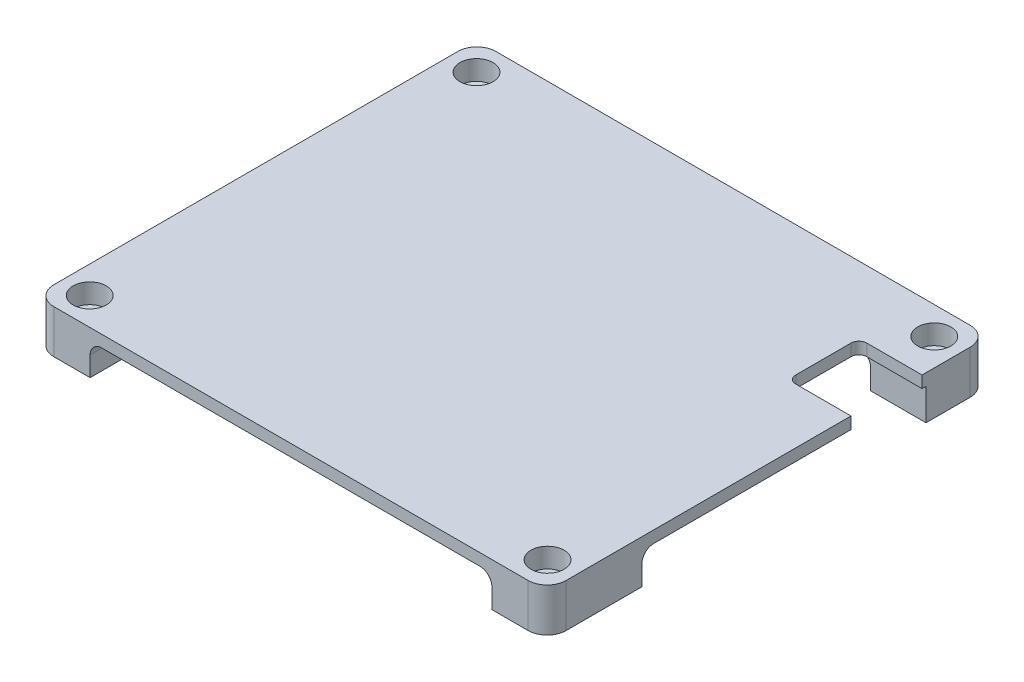
SolidWorks part; units mm, degrees
ref_plane "Front Plane" through (0, 0, 0) normal (0, 0, 1) x (1, 0, 0)
ref_plane "Top Plane" through (0, 0, 0) normal (0, 1, 0) x (1, 0, 0)
ref_plane "Right Plane" through (0, 0, 0) normal (1, 0, 0) x (0, 0, -1)
sketch "Sketch2" plane through (0, 0, 0) normal (0, 1, 0) x (1, 0, 0)
  line L0 (-22.55, -25.6) -> (-22.55, 25.6) construction
  line L1 (40.05, -28.1) -> (-40.1, -28.1) construction
  line L2 (42.55, -25.6) -> (42.55, 25.6) construction
  line L3 (40.05, 28.1) -> (-40.1, 28.1) construction
  line L4 (-22.55, -25.6) -> (-22.55, 25.6) construction
  line L5 (40.05, -28.1) -> (-20.05, -28.1) construction
  line L6 (42.55, -25.6) -> (42.55, 25.6) construction
  line L7 (40.05, 28.1) -> (-20.05, 28.1) construction
  line L8 (-22.45, -25.6) -> (-22.45, 25.6)
  line L9 (40.05, 28) -> (-20.05, 28)
  line L10 (42.45, -25.6) -> (42.45, 25.6)
  line L11 (40.05, -28) -> (-20.05, -28)
  line L12 (-15.45, 47.3336) -> (-15.45, -46.9162) construction
  line L13 (35.45, 47.3336) -> (35.45, -43.2485) construction
  line L14 (35.45, 20) -> (42.45, 20)
  line L15 (35.45, 20) -> (35.45, 28)
  line L16 (-22.45, 20) -> (-15.45, 20)
  line L17 (-15.45, 20) -> (-15.45, 28)
  line L18 (-39.5, 28) -> (39.5, 28) construction
  line L19 (42.45, -16) -> (35.45, -16)
  line L20 (35.45, -16) -> (35.45, -28)
  line L21 (39.5, -28) -> (-39.5, -28) construction
  line L22 (-15.45, -28) -> (-15.45, -8)
  line L23 (-2.45, 7) -> (-22.45, 7)
  line L24 (-15.45, 26.75) -> (35.45, 26.75)
  line L25 (34.45, 19.5) -> (42.45, 19.5)
  line L26 (34.45, 19.5) -> (34.45, 10.5)
  line L27 (34.45, 10.5) -> (42.45, 10.5)
  line L29 (9.45, -3) -> (27.45, -3)
  line L30 (9.45, -3) -> (9.45, -18)
  line L31 (9.45, -18) -> (27.45, -18)
  line L32 (27.45, -3) -> (27.45, -18)
  line L35 (-15.45, -8) -> (-2.45, -8)
  line L36 (-2.45, 7) -> (-2.45, -8)
  arc A0 (-22.55, -25.6) -> (-20.05, -28.1) centre (-20.05, -25.6) ccw construction
  arc A1 (40.05, -28.1) -> (42.55, -25.6) centre (40.05, -25.6) ccw construction
  arc A2 (42.55, 25.6) -> (40.05, 28.1) centre (40.05, 25.6) ccw construction
  arc A3 (-20.05, 28.1) -> (-22.55, 25.6) centre (-20.05, 25.6) ccw construction
  arc A4 (-22.55, -25.6) -> (-20.05, -28.1) centre (-20.05, -25.6) ccw construction
  arc A5 (40.05, -28.1) -> (42.55, -25.6) centre (40.05, -25.6) ccw construction
  arc A6 (42.55, 25.6) -> (40.05, 28.1) centre (40.05, 25.6) ccw construction
  arc A7 (-20.05, 28.1) -> (-22.55, 25.6) centre (-20.05, 25.6) ccw construction
  arc A8 (-20.05, 28) -> (-22.45, 25.6) centre (-20.05, 25.6) ccw
  arc A9 (42.45, 25.6) -> (40.05, 28) centre (40.05, 25.6) ccw
  arc A10 (40.05, -28) -> (42.45, -25.6) centre (40.05, -25.6) ccw
  arc A11 (-22.45, -25.6) -> (-20.05, -28) centre (-20.05, -25.6) ccw
  circle A12 centre (-19, -24.5) radius 1.35 construction
  circle A13 centre (39, -24.5) radius 1.35 construction
  circle A14 centre (39, 24.5) radius 1.35 construction
  circle A15 centre (-19, 24.5) radius 1.35 construction
  circle A16 centre (-19, -24.5) radius 1.35
  circle A17 centre (39, -24.5) radius 1.35
  circle A18 centre (39, 24.5) radius 1.35
  circle A19 centre (-19, 24.5) radius 1.35
  dimension "D2" = 7
  dimension "D3" = 7
  dimension "D4" = 8
  dimension "D5" = 12
  dimension "D6" = 35
  dimension "D7" = 8.5
  dimension "D8" = 17.5
  dimension "D9" = 8
  dimension "D10" = 10
  dimension "D11" = 25
  dimension "D12" = 15
  dimension "D13" = 33
  dimension "D14" = 20
  dimension "D15" = 20
  dimension "D16" = 1.25
  dimension "D1" = 0.1
extrude "Boss-Extrude1" add sketch "Sketch2" along normal up to surface (5.5 mm away) from offset 0 contours L9 A8 L8 L16 L17 | L8 A11 L11 L22 L23 | L10 A9 L9 L15 L14 | L11 A10 L10 L19 L20 | L32 L29 L30 L31 | L17 L24 L15 L9 region at (-14.4378, 0, 5.7634) region at (-22.3437, 0, -22.8) region at (38.8987, 0, 21.7265) region at (10, 0, -27.375) region at (35.5563, 0, -27.375) region at (18.45, 0, 10.5)
extrude "Boss-Extrude2" add sketch "Sketch2<3>" along normal up to surface (5.5 mm away) from offset 4 contours L23 L36 L35 L22 L11 L20 L19 L10 L27 L26 L25 L14 L15 L9 L17 L16 L8 L29 L32 L31 L30 region at (11.5529, 0, -0.7109) up to face at (-19, 5.5, 25.85)
sketch "Sketch2<3>" plane through (0, 0, 0) normal (0, 1, 0) x (1, 0, 0) same geometry as "Sketch2"
sketch "Sketch3" plane through (0, 5.5, 0) normal (0, 1, 0) x (1, 0, 0)
  circle A0 centre (39, -24.5) radius 2.1
  circle A1 centre (-19, -24.5) radius 2.1
  circle A2 centre (39, 24.5) radius 2.1
  circle A3 centre (-19, 24.5) radius 2.1
  circle M17 centre (-19, 24.5) radius 1.35
  circle M22 centre (-19, -24.5) radius 1.35
  circle M23 centre (39, 24.5) radius 1.35
  circle M24 centre (39, -24.5) radius 1.35
  dimension "D1" = 4.2
extrude "Cut-Extrude1" cut sketch "Sketch3" against normal blind 2.5 contours A2 M23 | A1 M22 | A0 M24 | A3 region at (36.9594, 5.5, 24.5) region at (-21.0406, 5.5, 24.5) region at (36.9594, 5.5, -24.5)
extrude "Cut-Extrude2" cut sketch "Sketch3<3>" along normal blind 0.5 from surface contours A3 M17 | A2 M23 | A0 M24 | A1 M22 region at (36.9594, 5.5, 24.5) region at (-21.0406, 5.5, 24.5) region at (36.9594, 5.5, -24.5) region at (-21.0406, 5.5, -24.5) starting at face at (-19, 0, 25.85)
sketch "Sketch3<3>" plane through (0, 5.5, 0) normal (0, 1, 0) x (1, 0, 0) same geometry as "Sketch3"
fillet "Fillet1" radius 1.5 25 edges at (-12.45, 4, -7) (-2.45, 4, 0.5) (38.95, 4, 16) (35.45, 2, 16) (35.45, 4, 22) (35.45, 4, -23.375) (-15.45, 2, -20) (-15.45, 4, -23.375) (-18.95, 4, -20) (-2.45, 2, -7) (-2.45, 2, 8) (-8.95, 4, 8) (-15.45, 4, 18) (-15.45, 2, 8) (18.45, 4, 18) (9.45, 4, 10.5) (27.45, 4, 10.5) (18.45, 4, 3) (27.45, 2, 18) (27.45, 2, 3) (9.45, 2, 3) (9.45, 2, 18) (35.45, 2, -26.75) (-15.45, 2, -26.75) (10, 4, -26.75)
fillet "Fillet2" radius 1 2 edges at (34.45, 4.75, -10.5) (34.45, 4.75, -19.5)
